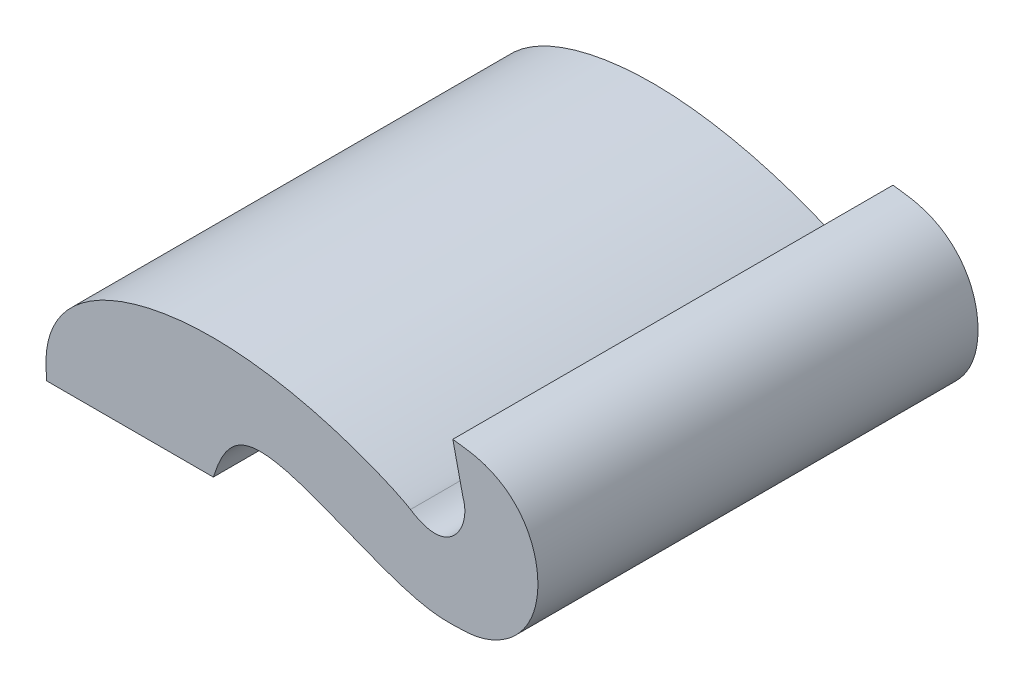
SolidWorks part; units mm, degrees
ref_plane "Front Plane" through (0, 0, 0) normal (0, 0, 1) x (1, 0, 0)
ref_plane "Top Plane" through (0, 0, 0) normal (0, 1, 0) x (1, 0, 0)
ref_plane "Right Plane" through (0, 0, 0) normal (1, 0, 0) x (0, 0, -1)
sketch "Sketch2" plane through (0, 0, 0) normal (0, 0, 1) x (1, 0, 0)
  line L0 (0, 0) -> (150, 0)
  line L3 (406.772, 97.0854) -> (396.5724, 142.4737)
  line L5 (-9.4111, -10) -> (157.1504, -10)
  line L7 (329.904, 5.8769) -> (329.904, -10.1082)
  line L8 (0, 0) -> (0, -10)
  line L9 (150, 0) -> (150, -10)
  line L10 (329.904, 5.8769) -> (469.904, 5.8769)
  line L16 (416.4137, 99.7898) -> (409.4945, 130.5802)
  spline S0 degree 3 poles (150, 0) (176.7705, 78.3344) (240.5426, 39.0906) (329.904, 5.8769) knots 0 0 0 0 1 1 1 1
  spline S1 degree 3 poles (0, 0) (-4.0791, 67.1634) (172.0353, 138.1381) (338.303, 59.3343) (348.714, 52.2038) knots 0 0 0 0 0.416096 1 1 1 1
  spline S2 degree 3 poles (329.904, 5.8769) (371.9205, -9.4009) (391.2289, -8.2029) (433.7919, -7.3158) (490.1519, 32.2021) (462.7003, 123.1801) (409.4945, 130.5802) knots 0 0 0 0 0.21951 0.282428 0.629183 1 1 1 1
  spline S3 degree 3 poles (348.714, 52.2038) (395.8995, 21.2633) (427.2798, 67.6356) (416.4137, 99.7898) knots 0 0 0 0 1 1 1 1
  spline S4 degree 1 poles (326.4534, -3.509) (396.5724, 142.4737) knots 0 0 1 1 construction
  spline S5 degree 1 poles (354.2681, 60.5201) (406.772, 97.0854) knots 0 0 1 1 construction
  spline S6 degree 1 poles (-9.4111, -10) (354.2681, 60.5201) knots 0 0 1 1 construction
  spline S7 degree 1 poles (157.1504, -10) (326.4534, -3.509) knots 0 0 1 1 construction
  spline S8 degree 3 poles (326.4534, -3.509) (327.232, -3.7921) (328.804, -4.3595) (331.8456, -5.4395) (335.5308, -6.7153) (339.7521, -8.1239) (345.1314, -9.8484) (351.4063, -11.7264) (358.2847, -13.5746) (364.5764, -15.0541) (372.2657, -16.5836) (380.7136, -17.7535) (389.386, -18.2592) (395.6216, -18.2124) (400.1796, -18.0772) (404.4645, -17.9464) (409.0789, -17.8089) (414.0105, -17.4137) (419.1685, -16.7415) (425.583, -15.3567) (433.1916, -12.8539) (443.0843, -8.4014) (454.7573, -0.7552) (466.8348, 11.7444) (474.5017, 24.8778) (478.7118, 36.8802) (481.4853, 49.836) (482.073, 67.3147) (477.6764, 88.9062) (469.0604, 106.0447) (458.7872, 118.1919) (450.9158, 124.8722) (443.7471, 129.5199) (437.9394, 132.623) (431.7057, 135.312) (426.1604, 137.1844) (421.5168, 138.4489) (417.9288, 139.278) (414.8582, 139.8664) (412.6528, 140.2251) (411.5536, 140.3888) (410.8984, 140.4814) (410.3311, 140.56) (409.6014, 140.6616) (408.4454, 140.8224) (406.417, 141.1045) (402.3641, 141.6682) (398.8889, 142.1515) (396.5724, 142.4737) knots -0.000058 -0.000058 -0.000058 -0.000058 0.003978 0.008014 0.016087 0.024159 0.032232 0.048377 0.064522 0.080667 0.096812 0.129102 0.161392 0.193682 0.209827 0.225972 0.258262 0.274407 0.290551 0.322841 0.355131 0.387421 0.452001 0.516581 0.581161 0.613451 0.645741 0.710321 0.774901 0.839481 0.871771 0.904061 0.920206 0.936351 0.952496 0.968641 0.976713 0.984786 0.992858 0.996894 0.998912 0.999921 1.000931 1.002949 1.004967 1.009003 1.017075 1.03322 1.03322 1.03322 1.03322
  spline S9 degree 3 poles (406.772, 97.0854) (406.8147, 96.9592) (406.8808, 96.7634) (406.9603, 96.5284) (407.0188, 96.3525) (407.0972, 96.1113) (407.215, 95.7348) (407.3567, 95.257) (407.5681, 94.4873) (407.805, 93.5115) (408.125, 91.9249) (408.414, 89.8971) (408.7509, 84.919) (407.9051, 77.1507) (404.0456, 67.3554) (397.8934, 59.3096) (391.3598, 54.7826) (385.3776, 52.6726) (380.4334, 51.9029) (374.9274, 52.0657) (369.7913, 53.1366) (365.3341, 54.6711) (361.821, 56.1891) (358.7478, 57.7885) (356.2214, 59.2715) (354.9086, 60.1011) (354.2681, 60.5201) knots 0.000566 0.000566 0.000566 0.000566 0.00449 0.006452 0.008414 0.012338 0.016262 0.024111 0.031959 0.047656 0.063352 0.094746 0.126139 0.251712 0.377286 0.502859 0.628433 0.691219 0.754006 0.816793 0.87958 0.910973 0.942366 0.97376 0.989456 1.005153 1.005153 1.005153 1.005153
  spline S10 degree 3 poles (354.2681, 60.5201) (353.7778, 60.8525) (352.8126, 61.4618) (351.1056, 62.4562) (349.1056, 63.5524) (346.0118, 65.1705) (341.3339, 67.4815) (334.4504, 70.662) (326.3592, 74.1725) (314.0547, 79.1833) (296.0176, 85.8541) (270.7383, 93.8182) (242.4468, 101.0396) (211.7654, 106.8106) (179.311, 110.411) (145.71, 111.1185) (111.557, 108.1512) (78.4194, 101.153) (47.8685, 89.748) (25.8852, 76.1007) (11.3325, 62.3189) (2.2456, 50.4709) (-3.5138, 39.3248) (-6.8611, 29.6872) (-8.7057, 22.118) (-9.8542, 14.2283) (-10.1759, 8.0831) (-10.1601, 3.8994) (-10.1147, 2.1376) (-10.0557, 0.7283) (-10.0079, -0.1764) (-9.9664, -0.8562) (-9.928, -1.489) (-9.8594, -2.6184) (-9.7621, -4.2204) (-9.606, -6.7901) (-9.4891, -8.7158) (-9.4111, -10) knots -0.019399 -0.019399 -0.019399 -0.019399 -0.003487 0.012424 0.028336 0.044247 0.07607 0.107894 0.139717 0.17154 0.235186 0.298833 0.362479 0.426125 0.489771 0.553418 0.617064 0.68071 0.744357 0.808003 0.839826 0.871649 0.903473 0.919384 0.935296 0.951207 0.967119 0.971097 0.975075 0.977064 0.979053 0.980047 0.981041 0.98303 0.987008 0.990986 0.998942 0.998942 0.998942 0.998942
  spline S11 degree 3 poles (157.1504, -10) (157.5808, -8.7406) (158.2285, -6.845) (158.9767, -4.6565) (159.4149, -3.3729) (159.8133, -2.2126) (160.3226, -0.7859) (161.1491, 1.4276) (162.6325, 5.1335) (164.8479, 9.9494) (167.6414, 14.9946) (170.5485, 19.3421) (174.5547, 24.2717) (179.7753, 28.9481) (186.4988, 32.7053) (194.0417, 34.9834) (202.7073, 35.8756) (215.8671, 35.2151) (231.3155, 31.8516) (248.6881, 26.3429) (262.6119, 21.3348) (277.3759, 15.6424) (290.3447, 10.4957) (301.103, 6.2371) (309.3589, 2.9983) (316.3955, 0.2818) (322.1096, -1.8866) (325.0076, -2.9716) (326.4534, -3.509) knots -0.028792 -0.028792 -0.028792 -0.028792 -0.012715 -0.004677 -0.000657 0.003362 0.0114 0.019439 0.035515 0.067669 0.099823 0.131976 0.16413 0.228437 0.292744 0.357052 0.421359 0.485666 0.614281 0.678588 0.742895 0.807202 0.87151 0.903663 0.935817 0.967971 0.984047 1.000124 1.000124 1.000124 1.000124
  point P16 (464.2459, 43.7443)
  point P20 (469.904, 43.7443)
  point P21 (406.772, -7.8603)
  dimension "D1" = 180
  dimension "D2" = 150
  dimension "D3" = 10
  dimension "D4" = 50
extrude "Boss-Extrude1" add sketch "Sketch2" against normal blind 430 contours S9 S10 L5 L8 S1 S3 L16 S2 L7 S8 L3 | L9 L0 L8 L5 | L5 S11 S8 L7 S0 L9 | S3 S1 L0 S0 S2 L16 | L7 S8 L10 S2 | L10 S2 region at (229.7494, 50.1789, 0) region at (75, -5, 0) region at (-5.1482, -5, 0) region at (231.3137, 39.9138, 0) region at (388.4941, -9.4714, 0) region at (391.8738, 0.1154, 0)
extrude "Cut-Extrude1" cut sketch "Sketch2<5>" against normal blind 400 contours S3 S1 L0 S0 S2 L16 region at (229.7494, 50.1789, 0)
sketch "Sketch2<5>" plane through (0, 0, 0) normal (0, 0, 1) x (1, 0, 0) same geometry as "Sketch2"
extrude "Boss-Extrude3" add sketch "Sketch2<6>" along normal blind 10 contours L9 L0 L8 L5 | S11 S8 L3 S9 S10 L5 region at (75, -5, 0)
sketch "Sketch2<6>" plane through (0, 0, 0) normal (0, 0, 1) x (1, 0, 0) same geometry as "Sketch2"
sketch "Sketch3" plane through (0, -10, 0) normal (0, -1, 0) x (1, 0, 0)
  line L0 (0, 0) -> (0, -400)
  line L1 (0, 0) -> (120, 0)
  line L2 (120, 0) -> (120, -400)
  line L3 (120, -400) -> (0, -400)
extrude "Cut-Extrude2" cut sketch "Sketch3" against normal blind 10
sketch "Sketch4" plane through (407.9862, 91.6823, 0) normal (-0.9757, -0.2193, 0) x (0, 0, 1)
  line L0 (0, 5.5378) -> (0, 10.5378)
  line L1 (0, 52.0581) -> (0, 47.0581)
  line L2 (-430, 5.5378) -> (10, 5.5378) construction
  line L3 (-400.3409, 47.0581) -> (-400.3409, 10.5395)
  line L4 (-400.3409, 10.5395) -> (0, 10.5395)
  line L5 (0, 10.5395) -> (0, 47.0581)
  line L6 (0, 47.0581) -> (-400.3409, 47.0581)
  line L7 (-430, 52.0581) -> (10, 52.0581) construction
  point P13 (0, 47.301)
extrude "Cut-Extrude3" cut sketch "Sketch4" against normal blind 10 contours L5 L6 L3 L4 region at (401.672, 119.7804, -200.1705)
